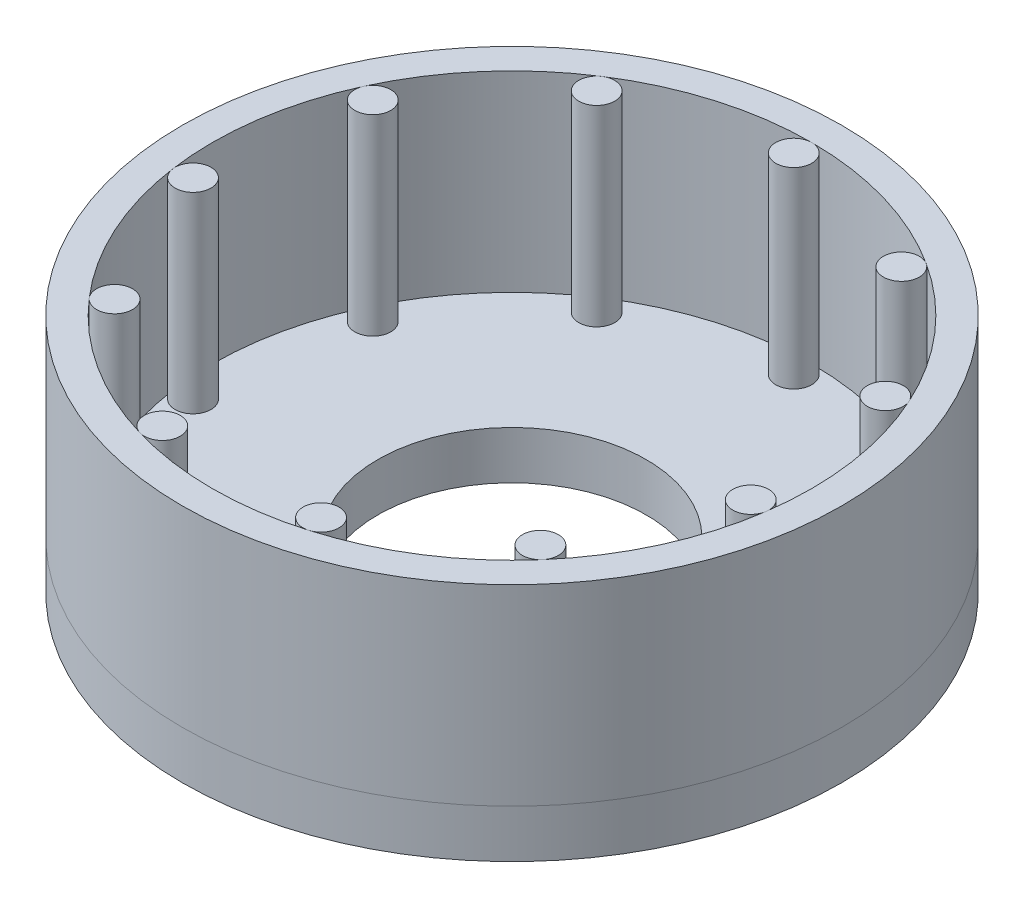
SolidWorks part; units mm, degrees
ref_plane "Front Plane" through (0, 0, 0) normal (0, 0, 1) x (1, 0, 0)
ref_plane "Top Plane" through (0, 0, 0) normal (0, 1, 0) x (1, 0, 0)
ref_plane "Right Plane" through (0, 0, 0) normal (1, 0, 0) x (0, 0, -1)
sketch "Sketch1" plane through (0, 0, 0) normal (0, 1, 0) x (1, 0, 0)
  line L0 (0, 0) -> (0, 23.5) construction
  line L1 (0, 0) -> (-15.5, 0) construction
  line L2 (-15.5, 0) -> (-15.5, 15.5) construction
  circle A0 centre (0, 0) radius 27.5
  circle A1 centre (0, 23.5) radius 1.5
  circle A2 centre (12.7051, 19.7695) radius 1.5
  circle A3 centre (21.3764, 9.7623) radius 1.5
  circle A4 centre (23.2608, -3.3444) radius 1.5
  circle A5 centre (17.7601, -15.3892) radius 1.5
  circle A6 centre (6.6207, -22.5481) radius 1.5
  circle A7 centre (-6.6207, -22.5481) radius 1.5
  circle A8 centre (-17.7601, -15.3892) radius 1.5
  circle A9 centre (-23.2608, -3.3444) radius 1.5
  circle A10 centre (-21.3764, 9.7623) radius 1.5
  circle A11 centre (-12.7051, 19.7695) radius 1.5
  circle A12 centre (0, 0) radius 25
  circle A13 centre (0, 0) radius 11.2
  point P6 (0, 0)
  point P27 (0, 0)
  dimension "D1" = 55
  dimension "D4" = 3
  dimension "D6" = 50
  dimension "D7" = 22.4
  dimension "D2" = 23.5
  dimension "D3" = 23.5
  dimension "D8" = 15.5
  dimension "D5" = 11
extrude "Boss-Extrude1" add sketch "Sketch1" along normal blind 16 contours A9 | A8 | A7 | A6 | A5 | A3 | A2 | A1 | A11 | A10 | A0 A12 A8 | A4 region at (-26.7222, 0, 0) region at (0, 0, -23.5) region at (-12.7051, 0, -19.7695) region at (-21.3764, 0, -9.7623) region at (-23.2608, 0, 3.3444) region at (-17.7601, 0, 15.3892) region at (-6.6207, 0, 22.5481) region at (6.6207, 0, 22.5481) region at (17.7601, 0, 15.3892) region at (21.3764, 0, -9.7623) region at (12.7051, 0, -19.7695)
extrude "Boss-Extrude2" add sketch "Sketch1<3>" against normal blind 4 contours A0
sketch "Sketch1<3>" plane through (0, 0, 0) normal (0, 1, 0) x (1, 0, 0) same geometry as "Sketch1"
extrude "Cut-Extrude1" cut sketch "Sketch1<5>" against normal through all both and the other way through all contours A13 region at (0, 0, 0)
sketch "Sketch1<5>" plane through (0, 0, 0) normal (0, 1, 0) x (1, 0, 0) same geometry as "Sketch1"
ref_plane "Plane1" through (0, 10, 0) normal (0, 1, 0) x (1, 0, 0)
